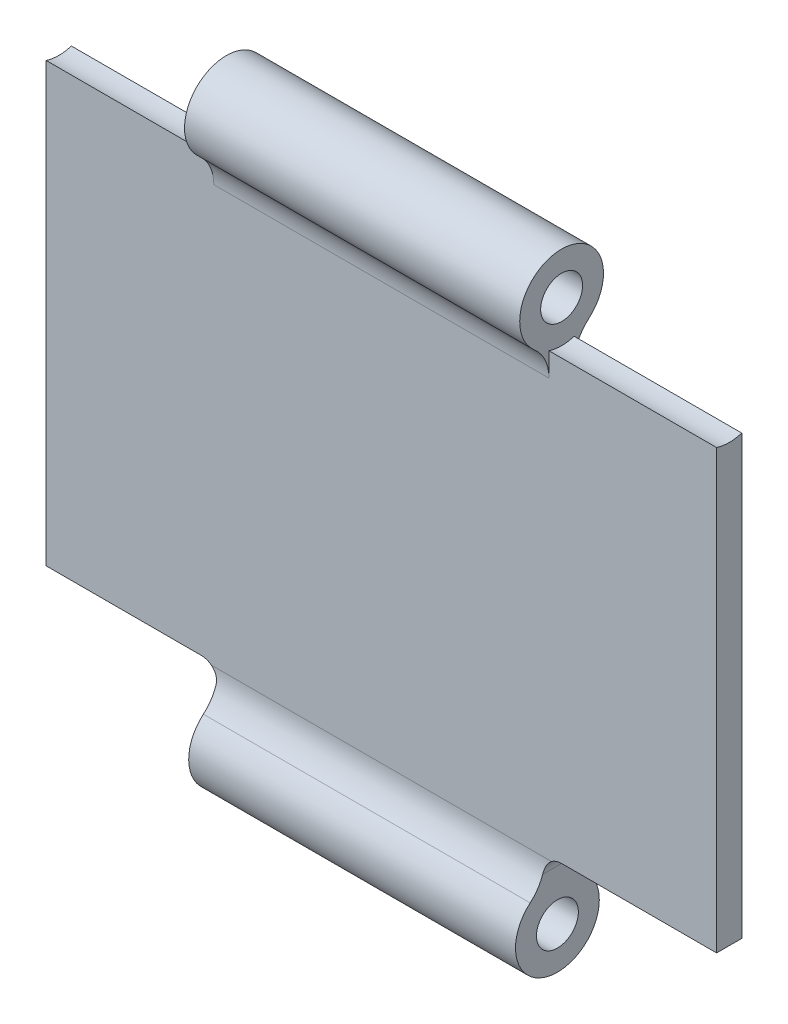
SolidWorks part; units mm, degrees
ref_plane "前视基准面" through (0, 0, 0) normal (0, 0, 1) x (1, 0, 0)
ref_plane "上视基准面" through (0, 0, 0) normal (0, 1, 0) x (1, 0, 0)
ref_plane "右视基准面" through (0, 0, 0) normal (1, 0, 0) x (0, 0, -1)
sketch "草图1" plane through (0, 0, 0) normal (0, 0, 1) x (1, 0, 0)
  line L1 (-40, -32.5) -> (40, -32.5)
  line L2 (-40, -32.5) -> (-40, 32.5)
  line L3 (-40, 32.5) -> (40, 32.5)
  line L4 (40, -32.5) -> (40, 32.5)
  line L5 (-40, -32.5) -> (40, 32.5) construction
  line L6 (-40, 32.5) -> (40, -32.5) construction
  point P0 (0, 0)
  dimension "D1" = 65
  dimension "D2" = 80
extrude "凸台-拉伸1" add sketch "草图1" along normal blind 3 contours L3 L4 L1 L2
sketch "草图3" plane through (0, 0, 3) normal (0, 0, 1) x (1, 0, 0)
  line L0 (-40, -24.5) -> (-19.5, -24.5)
  line L1 (-40, -32.5) -> (-40, 32.5) construction
  line L2 (-19.5, -24.5) -> (-19.5, -32.5)
  line L3 (-40, -32.5) -> (40, -32.5) construction
  line L4 (0, 0) -> (0, -38.2437) construction
  line L5 (40, -24.5) -> (19.5, -24.5)
  line L6 (19.5, -24.5) -> (19.5, -32.5)
  line L7 (-19.5, -32.5) -> (19.5, -32.5)
  dimension "D1" = 8
  dimension "D2" = 39
extrude "切除-拉伸1" cut sketch "草图3" against normal blind 3 and the other way through all
sketch "草图4" plane through (0, 0, 0) normal (1, 0, 0) x (0, 0, -1)
  line L0 (-3, -32.5) -> (0, -32.5) construction
  circle A0 centre (-1.5, -32.5) radius 5
  dimension "D1" = 10
extrude "凸台-拉伸2" add sketch "草图4" along normal up to surface and the other way up to surface up to face at (19.5, -28.5, 1.5) other way up to face at (-19.5, -28.5, 1.5)
sketch "草图6" plane through (-19.5, 0, 0) normal (-1, 0, 0) x (0, 0, 1)
  circle A0 centre (1.5, -32.5) radius 2.5
  dimension "D1" = 5
extrude "切除-拉伸3" cut sketch "草图6" against normal through all
fillet "圆角1" radius 5 2 edges at (0, -27.7303, 0) (0, -27.7303, 3) tangent propagation no
sketch "草图8" plane through (0, 0, 0) normal (1, 0, 0) x (0, 0, -1)
  line L0 (-3, 32.5) -> (0, 32.5) construction
  circle A0 centre (-1.5, 32.5) radius 5
  dimension "D1" = 10
extrude "凸台-拉伸3" add sketch "草图8" along normal mid plane 40
sketch "草图9" plane through (20, 0, 0) normal (1, 0, 0) x (0, 0, -1)
  line L0 (-3, 32.5) -> (0, 32.5) construction
  circle A0 centre (-1.5, 32.5) radius 5
extrude "切除-拉伸4" cut sketch "草图9" along normal through all
mirror "镜向1" about plane through (0, 0, 0) normal (1, 0, 0) of "切除-拉伸4"
fillet "圆角2" radius 5 2 edges at (0, 27.7303, 3) (0, 27.7303, 0)
sketch "草图10" plane through (20, 0, 0) normal (1, 0, 0) x (0, 0, -1)
  circle A0 centre (-1.5, 32.5) radius 2.5
  arc A1 (1.75, 28.7003) -> (-4.75, 28.7003) centre (-1.5, 32.5) ccw construction
  dimension "D1" = 5
extrude "切除-拉伸5" cut sketch "草图10" against normal through all
fillet "圆角3" radius 2 2 edges at (19.5, -24.5, 1.5) (-19.5, -24.5, 1.5)
